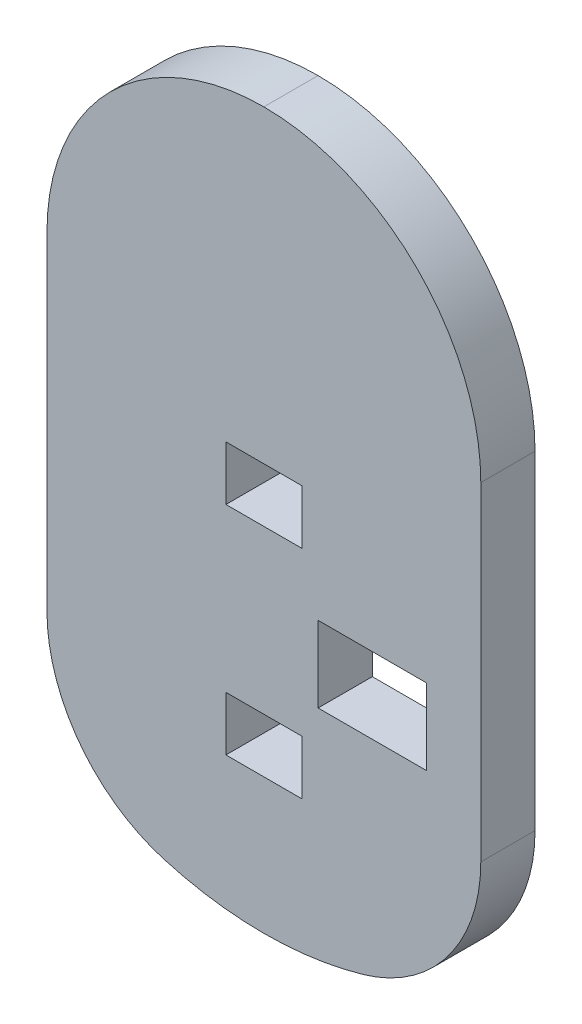
SolidWorks part; units mm, degrees
material "Acrylic (Medium-high impact)"
ref_plane "Front Plane" through (0, 0, 0) normal (0, 0, 1) x (1, 0, 0)
ref_plane "Top Plane" through (0, 0, 0) normal (0, 1, 0) x (1, 0, 0)
ref_plane "Right Plane" through (0, 0, 0) normal (1, 0, 0) x (0, 0, -1)
sketch "Sketch1" plane through (0, 0, 0) normal (0, 0, 1) x (1, 0, 0)
  circle A0 centre (0, 0) radius 33
  point P0 (0, 0)
  dimension "D1" = 66
extrude "Boss-Extrude1" add sketch "Sketch1" along normal blind 5
sketch "Sketch10" plane through (0, 0, 5) normal (0, 0, 1) x (1, 0, 0)
  line L0 (-20, 26.2488) -> (-20, -26.2488)
  line L1 (20, 26.2488) -> (20, -26.2488)
  circle A0 centre (0, 0) radius 33 construction
  arc A1 (-20, 26.2488) -> (-20, -26.2488) centre (0, 0) ccw
  arc A2 (20, -26.2488) -> (20, 26.2488) centre (0, 0) ccw
  dimension "D1" = 20
  dimension "D2" = 40
extrude "Cut-Extrude3" cut sketch "Sketch10" against normal blind 10
fillet "Fillet2" radius 20 2 edges at (-20, 26.2488, 2.5) (20, 26.2488, 2.5)
fillet "Fillet3" radius 15 2 edges at (20, -26.2488, 2.5) (-20, -26.2488, 2.5)
sketch "Sketch11" plane through (0, 0, 5) normal (0, 0, 1) x (1, 0, 0)
  line L1 (-3.5, 4.5) -> (3.5, 4.5)
  line L2 (-3.5, 4.5) -> (-3.5, -0.5)
  line L3 (-3.5, -0.5) -> (3.5, -0.5)
  line L4 (3.5, 4.5) -> (3.5, -0.5)
  line L5 (-3.5, -15.5) -> (3.5, -15.5)
  line L6 (-3.5, -15.5) -> (-3.5, -20.5)
  line L7 (-3.5, -20.5) -> (3.5, -20.5)
  line L8 (3.5, -15.5) -> (3.5, -20.5)
  point P10 (0, -0.5)
  dimension "D1" = 7
  dimension "D2" = 5
  dimension "D3" = 28.5
  dimension "D4" = 15
extrude "Cut-Extrude4" cut sketch "Sketch11" against normal blind 10
sketch "Sketch4" plane through (0, 0, 5) normal (0, 0, 1) x (1, 0, 0)
  line L1 (-11, 4.5) -> (11, 4.5)
  line L2 (-11, 4.5) -> (-11, -0.5)
  line L3 (-11, -0.5) -> (11, -0.5)
  line L4 (11, 4.5) -> (11, -0.5)
  line L5 (-11, 4.5) -> (11, -0.5) construction
  line L6 (-11, -0.5) -> (11, 4.5) construction
  point P0 (0, 2)
  dimension "D1" = 22
  dimension "D2" = 5
  dimension "D3" = 2
extrude "Boss-Extrude2" [suppressed] add sketch "Sketch4" along normal blind 35
sketch "Sketch5" [suppressed] plane through (0, 4.5, 0) normal (0, 1, 0) x (1, 0, 0)
  line L1 (-6, -11) -> (6, -11)
  line L2 (-6, -11) -> (-6, -34)
  line L3 (-6, -34) -> (6, -34)
  line L4 (6, -11) -> (6, -34)
  line L5 (-6, -11) -> (6, -34) construction
  line L6 (-6, -34) -> (6, -11) construction
  line L7 (-11, -40) -> (-11, -5) construction
  line L8 (11, -40) -> (-11, -40) construction
  point P0 (0, -22.5)
  point P10 (-11, -22.5)
  point P12 (0, -40)
  dimension "D1" = 12
  dimension "D2" = 23
extrude "Cut-Extrude1" [suppressed] cut sketch "Sketch5" against normal blind 5
sketch "Sketch6" [suppressed] plane through (0, 4.5, 0) normal (0, 1, 0) x (1, 0, 0)
  line L0 (0, -8) -> (0, -37) construction
  line L1 (-6, -11) -> (-6, -34) construction
  line L2 (-6, -34) -> (6, -34) construction
  circle A0 centre (0, -8) radius 1.25
  circle A1 centre (0, -37) radius 1.25
  point P4 (0, -22.5)
  point P7 (-6, -22.5)
  point P10 (0, -34)
  dimension "D1" = 2.5
  dimension "D2" = 29
extrude "Cut-Extrude2" [suppressed] cut sketch "Sketch6" against normal blind 5
sketch "Sketch7" [suppressed] plane through (0, 0, 40) normal (0, 0, 1) x (1, 0, 0)
  line L0 (11, -0.5) -> (11, 4.5) construction
  line L1 (-11, 4.5) -> (11, 4.5)
  line L2 (-11, 4.5) -> (-11, -15.5)
  line L3 (-11, -15.5) -> (11, -15.5)
  line L4 (11, 4.5) -> (11, -15.5)
  line L5 (11, -0.5) -> (11, 4.5) construction
  dimension "D1" = 20
extrude "Boss-Extrude3" [suppressed] add sketch "Sketch7" along normal blind 5
sketch "Sketch8" [suppressed] plane through (0, -15.5, 0) normal (0, -1, 0) x (1, 0, 0)
  line L1 (-11, 45) -> (11, 45)
  line L2 (-11, 45) -> (-11, 5)
  line L3 (-11, 5) -> (11, 5)
  line L4 (11, 45) -> (11, 5)
extrude "Boss-Extrude4" [suppressed] add sketch "Sketch8" along normal blind 5
sketch "Sketch9" [suppressed] plane through (0, -20.5, 0) normal (0, -1, 0) x (1, 0, 0)
  line L0 (-11, 5) -> (11, 5) construction
  circle A0 centre (0, 27.5) radius 3.75
  dimension "D1" = 7.5
  dimension "D2" = 22.5
extrude "Boss-Extrude5" [suppressed] add sketch "Sketch9" along normal blind 7
fillet "Fillet4" [suppressed] radius 0.5
sketch "Sketch12" plane through (0, 0, 5) normal (0, 0, 1) x (1, 0, 0)
  line L6 (-3.5, -0.5) -> (3.5, -0.5) construction
  line L7 (5, -5.5) -> (15, -5.5)
  line L8 (5, -5.5) -> (5, -12.5)
  line L9 (5, -12.5) -> (15, -12.5)
  line L10 (15, -5.5) -> (15, -12.5)
  line L11 (20, 13) -> (20, -17.2916) construction
  dimension "D1" = 10
  dimension "D2" = 7
  dimension "D3" = 5
  dimension "D4" = 5
extrude "Cut-Extrude5" cut sketch "Sketch12" against normal blind 10
